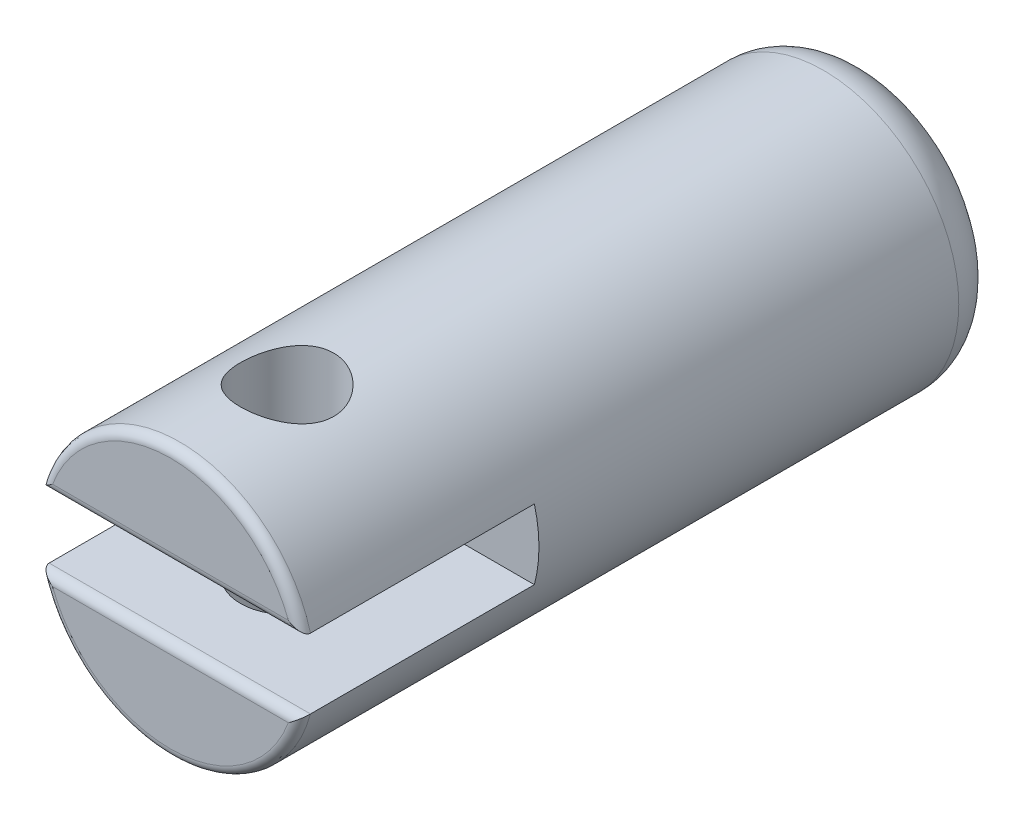
SolidWorks part; units mm, degrees
ref_plane "Front Plane" through (0, 0, 0) normal (0, 0, 1) x (1, 0, 0)
ref_plane "Top Plane" through (0, 0, 0) normal (0, 1, 0) x (1, 0, 0)
ref_plane "Right Plane" through (0, 0, 0) normal (1, 0, 0) x (0, 0, -1)
sketch "Sketch1" plane through (0, 0, 0) normal (0, 0, 1) x (1, 0, 0)
  circle A0 centre (0, 0) radius 2.9
  dimension "D1" = 5.8
extrude "Boss-Extrude1" add sketch "Sketch1" along normal blind 15
fillet "Fillet2" radius 1 1 edges at (2.9, 0, 0)
sketch "Sketch2" plane through (0, 0, 0) normal (0, 1, 0) x (1, 0, 0)
  line L0 (-2.9, -15) -> (2.9, -15) construction
  line L1 (-2.9, -15) -> (2.9, -15)
  line L2 (-2.9, -15) -> (-2.9, -10)
  line L3 (-2.9, -10) -> (2.9, -10)
  line L4 (2.9, -15) -> (2.9, -10)
  line L5 (2.9, -15) -> (2.9, -1) construction
  circle A0 centre (0, -12.5) radius 1
  point P4 (0, -15)
  point P8 (0, 0)
  point P13 (0, -12.7791)
  dimension "D2" = 2
  dimension "D1" = 5
  dimension "D3" = 2.5
extrude "Cut-Extrude1" cut sketch "Sketch2" against normal mid plane 1.5 contours A0 | L1 L4 L3 L2 A0 region at (-2.8234, 0, 12.5) region at (0, 0, 12.5)
extrude "Cut-Extrude2" cut sketch "Sketch2<3>" against normal through all both and the other way through all contours A0 region at (0, 0, 12.5)
sketch "Sketch2<3>" plane through (0, 0, 0) normal (0, 1, 0) x (1, 0, 0) same geometry as "Sketch2"
fillet "Fillet4" radius 0.2 4 edges at (0, -0.75, 15) (0, -2.9, 15) (0, 2.9, 15) (0, 0.75, 15)
